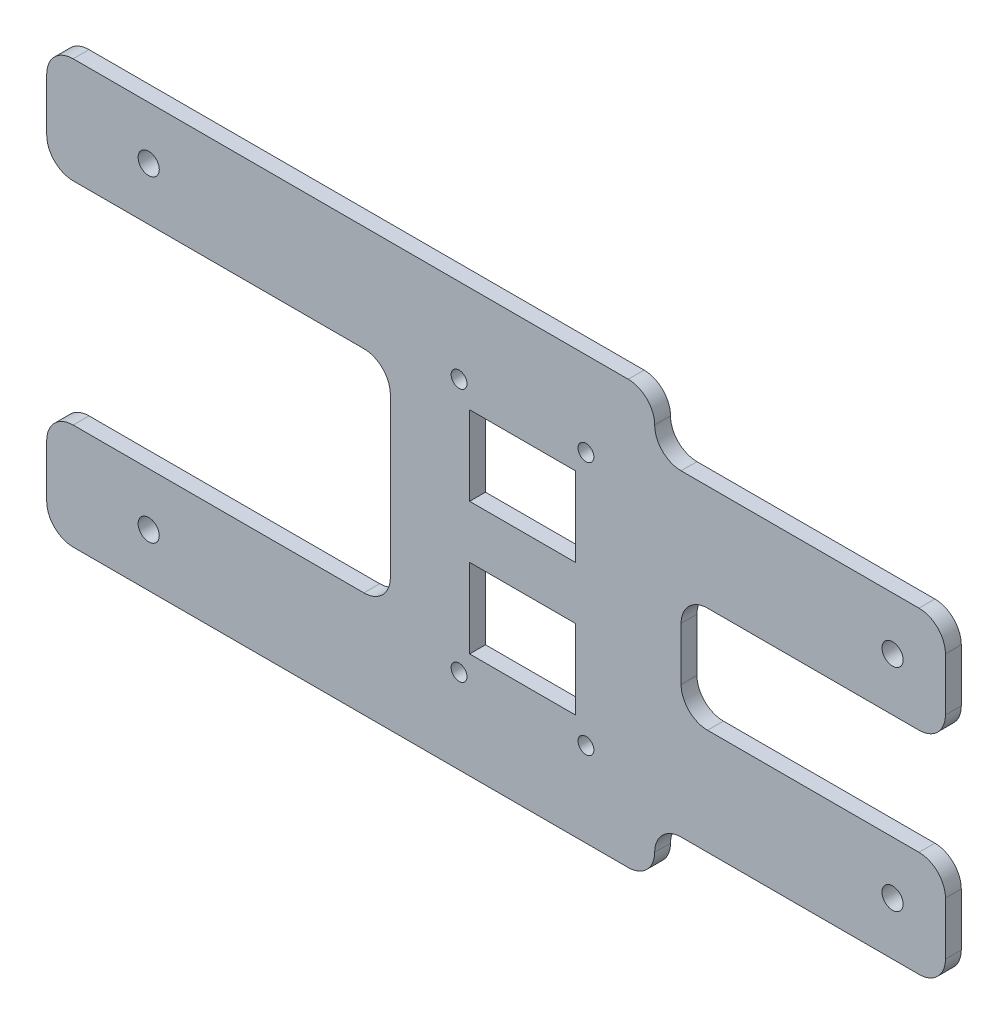
SolidWorks part; units mm, degrees
material "Caoba"
ref_plane "Alzado" through (0, 0, 0) normal (0, 0, 1) x (1, 0, 0)
ref_plane "Planta" through (0, 0, 0) normal (0, 1, 0) x (1, 0, 0)
ref_plane "Vista lateral" through (0, 0, 0) normal (1, 0, 0) x (0, 0, -1)
sketch "Croquis18" plane through (0, 0, 0) normal (0, 0, 1) x (1, 0, 0)
  line L1 (90, 0) -> (-90, 0) construction
  line L2 (0, 39) -> (0, -39) construction
  line L3 (90, -40) -> (-90, -40)
  line L4 (-10, -5) -> (10, -5)
  line L5 (-10, 20) -> (10, 20)
  line L6 (-10, 20) -> (-10, 5)
  line L7 (-10, 5) -> (10, 5)
  line L8 (10, 20) -> (10, 5)
  line L9 (10, -20) -> (10, -5)
  line L10 (-10, -20) -> (10, -20)
  line L11 (-10, -20) -> (-10, -5)
  line L12 (90, -40) -> (90, 40)
  line L13 (90, 40) -> (-90, 40)
  line L14 (-90, -40) -> (-90, 40)
  line L19 (-90, 20) -> (-25, 20)
  line L20 (-90, 20) -> (-90, -20)
  line L21 (-90, -20) -> (-25, -20)
  line L22 (-25, 20) -> (-25, -20)
  line L23 (90, 40) -> (25, 40)
  line L24 (90, 40) -> (90, 30)
  line L25 (90, 30) -> (25, 30)
  line L26 (25, 40) -> (25, 30)
  line L27 (90, -40) -> (25, -40)
  line L28 (90, -40) -> (90, -30)
  line L29 (90, -30) -> (25, -30)
  line L30 (25, -40) -> (25, -30)
  line L31 (90, 30) -> (80, 30)
  line L32 (90, 30) -> (90, -30)
  line L33 (90, -30) -> (80, -30)
  line L34 (80, 30) -> (80, -30)
  line L35 (80, 10) -> (30, 10)
  line L36 (80, 10) -> (80, -10)
  line L37 (80, -10) -> (30, -10)
  line L38 (30, 10) -> (30, -10)
  circle A0 centre (-12, 24) radius 1.5
  circle A1 centre (12, 24) radius 1.5
  circle A2 centre (-12, -24) radius 1.5
  circle A3 centre (12, -24) radius 1.5
  circle A4 centre (70, 20) radius 2
  circle A5 centre (70, -20) radius 2
  circle A6 centre (-70.71, -30) radius 2
  circle A7 centre (-70.71, 30) radius 2
  dimension "D1" = 48
  dimension "D2" = 24
  dimension "D3" = 48
  dimension "D4" = 24
  dimension "D5" = 3
  dimension "D6" = 3
  dimension "D7" = 3
  dimension "D8" = 3
  dimension "D9" = 180
  dimension "D10" = 12
  dimension "D11" = 12
  dimension "D12" = 0
  dimension "D18" = 24
  dimension "D19" = 24
  dimension "D33" = 40
  dimension "D34" = 4
  dimension "D35" = 4
  dimension "D36" = 4
  dimension "D37" = 60
  dimension "D38" = 4
  dimension "D39" = 10
  dimension "D40" = 19.29
  dimension "D41" = 19.29
  dimension "D42" = 20
  dimension "D43" = 10
  dimension "D44" = 10
  dimension "D45" = 10
  dimension "D46" = 10
  dimension "D13" = 15
  dimension "D14" = 20
  dimension "D15" = 10
  dimension "D16" = 0
  dimension "D17" = 5
  dimension "D20" = 90
  dimension "D21" = 39
  dimension "D22" = 78
  dimension "D23" = 80
  dimension "D24" = 40
  dimension "D25" = 10
  dimension "D26" = 65
  dimension "D27" = 40
  dimension "D28" = 10
  dimension "D29" = 65
  dimension "D30" = 20
  dimension "D31" = 65
  dimension "D32" = 10
  dimension "D47" = 50
extrude "Saliente-Extruir1" add sketch "Croquis18" along normal blind 3 contours L19 L22 L21 L14 L3 L12 L26 L13 A3 A2 A1 A0 L5 L8 L7 L6 L10 L11 L4 L9 region at (-3.7989, 0, 0)
fillet "Redondeo1" radius 5 16 edges at (25, -40, 1.5) (25, -30, 1.5) (25, 40, 1.5) (25, 30, 1.5) (-25, -20, 1.5) (-25, 20, 1.5) (-90, -40, 1.5) (-90, -20, 1.5) (-90, 20, 1.5) (-90, 40, 1.5) (80, 30, 1.5) (80, -30, 1.5) (30, -10, 1.5) (30, 10, 1.5) (80, -10, 1.5) (80, 10, 1.5)
